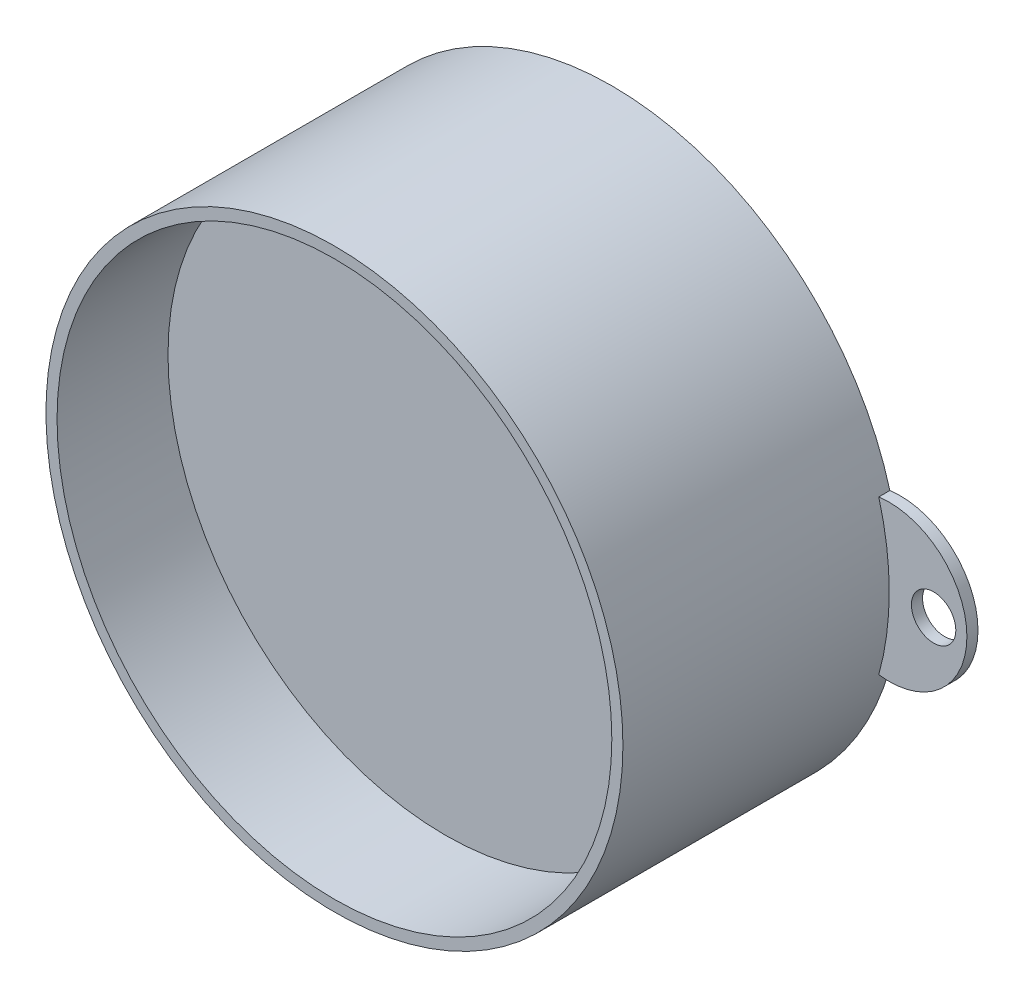
SolidWorks part; units mm, degrees
ref_plane "Plan de face" through (0, 0, 0) normal (0, 0, 1) x (1, 0, 0)
ref_plane "Plan de dessus" through (0, 0, 0) normal (0, 1, 0) x (1, 0, 0)
ref_plane "Plan de droite" through (0, 0, 0) normal (1, 0, 0) x (0, 0, -1)
sketch "Esquisse1" plane through (0, 0, 0) normal (0, 0, 1) x (1, 0, 0)
  line L0 (-26, 0) -> (26, 0) construction
  line L1 (0, 26) -> (0, -26) construction
  circle A0 centre (0, 0) radius 26
  circle A1 centre (-30, 0) radius 2
  arc A2 (-25.0577, 6.9363) -> (-25.0577, -6.9363) centre (-26, 0) ccw
  circle A3 centre (30, 0) radius 2
  arc A4 (25.0577, 6.9363) -> (25.0577, -6.9363) centre (26, 0) cw
  dimension "D1" = 52
  dimension "D2" = 4
  dimension "D4" = 7
  dimension "D3" = 4
extrude "Boss.-Extru.1" add sketch "Esquisse1" along normal blind 1 contours A0 | A0 A2 A1 | A4 A0 A3 region at (0, 0, 0) region at (25.9228, 3.5217, 0) region at (-26.161, 0, 0)
extrude "Boss.-Extru.2" add sketch "Esquisse1<3>" along normal blind 25 contours A0 region at (0, 0, 0)
sketch "Esquisse1<3>" plane through (0, 0, 0) normal (0, 0, 1) x (1, 0, 0) same geometry as "Esquisse1"
sketch "Esquisse2" plane through (0, 0, 25) normal (0, 0, 1) x (1, 0, 0)
  circle A5 centre (0, 0) radius 25
  circle A6 centre (0, 0) radius 25
  dimension "D2" = 1
extrude "Enlèv. mat.-Extru.1" cut sketch "Esquisse2" against normal blind 10
